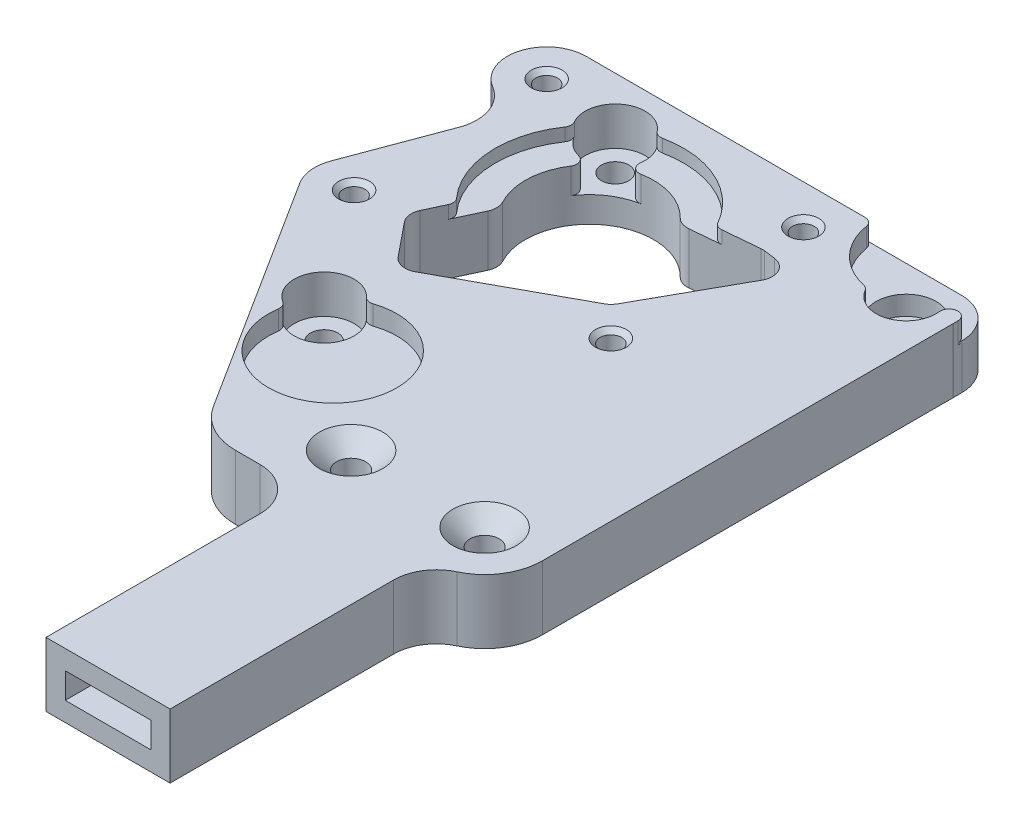
SolidWorks part; units mm, degrees
ref_plane "Front Plane" through (0, 0, 0) normal (0, 0, 1) x (1, 0, 0)
ref_plane "Top Plane" through (0, 0, 0) normal (0, 1, 0) x (1, 0, 0)
ref_plane "Right Plane" through (0, 0, 0) normal (1, 0, 0) x (0, 0, -1)
ref_plane "Plane1" through (0, 7.5, 0) normal (0, 1, 0) x (1, 0, 0)
sketch "Sketch1" plane through (0, 7.5, 0) normal (0, 1, 0) x (1, 0, 0)
  line L0 (33.5088, 30.3732) -> (33.4946, 33.0246)
  line L1 (28.8947, 37.6) -> (-15, 37.6)
  line L2 (-15.2354, 23.0047) -> (-20.1102, 9.9673)
  line L3 (-20.1102, 9.9673) -> (-10.6436, -4.9474)
  line L4 (-3.0147, -6.6193) -> (18.315, 7.1653)
  line L5 (18.315, 7.1653) -> (33.5088, 30.3732)
  line L6 (5.9537, 27.5611) -> (14.9094, 28.3729)
  line L7 (14.9094, 28.3729) -> (16.4399, 28.1735)
  line L8 (17.9289, 25.2174) -> (11.6276, 13.8992)
  line L9 (11.6276, 13.8992) -> (-4.6196, 5.0217)
  line L10 (-4.6196, 5.0217) -> (-9.6163, 11.1694)
  line L11 (-9.6163, 11.1694) -> (-6.1277, 18.6756)
  arc A0 (33.4946, 33.0246) -> (28.8947, 37.6) centre (28.8947, 33) ccw
  arc A1 (-15, 37.6) -> (-17.3569, 29.0497) centre (-15, 33) ccw
  arc A2 (-17.3569, 29.0497) -> (-15.2354, 23.0047) centre (-19.9187, 24.7558) cw
  arc A3 (-10.6436, -4.9474) -> (-3.0147, -6.6193) centre (-6, -2) ccw
  arc A4 (-6.1277, 18.6756) -> (5.9537, 27.5611) centre (0, 23) cw
  arc A5 (16.4399, 28.1735) -> (17.9289, 25.2174) centre (16.1815, 26.1903) cw
extrude "Boss-Extrude1" add sketch "Sketch1" against normal blind 7.5
sketch "Sketch2" plane through (0, 7.5, 0) normal (0, 1, 0) x (-1, 0, 0)
  line L0 (-33.4971, -32.5476) -> (-33.4946, -33.0246)
  arc A0 (-33.4946, -33.0246) -> (-33.4848, -32.699) centre (-28.8947, -33) cw
  arc A1 (-33.4848, -32.699) -> (-33.4971, -32.5476) centre (-32.4972, -32.5423) cw
extrude "Cut-Extrude1" cut sketch "Sketch2" against normal blind 2.45
sketch "Sketch3" plane through (0, 7.5, 0) normal (0, 1, 0) x (-1, 0, 0)
  line L0 (-28.8947, -37.6) -> (-18.4914, -37.6)
  arc A0 (-18.4914, -37.6) -> (-31.7305, -33.1844) centre (-25.9808, -38) ccw
  arc A1 (-31.7305, -33.1844) -> (-33.4848, -32.699) centre (-32.4972, -32.5423) cw
  arc A2 (-33.4848, -32.699) -> (-28.8947, -37.6) centre (-28.8947, -33) ccw
extrude "Cut-Extrude2" cut sketch "Sketch3" against normal blind 2.25
sketch "Sketch4" plane through (0, 7.5, 0) normal (0, 1, 0) x (-1, 0, 0)
  line L0 (-5.9537, -27.5611) -> (-9.8416, -27.9135)
  line L1 (7.7472, -15.191) -> (6.1277, -18.6756)
  arc A0 (-9.8416, -27.9135) -> (2.8936, -33.6126) centre (0, -23) ccw
  arc A1 (2.8936, -33.6126) -> (8.6833, -29.7528) centre (6, -32) ccw
  arc A2 (8.6833, -29.7528) -> (7.7472, -15.191) centre (0, -23) ccw
  arc A3 (6.1277, -18.6756) -> (-5.9537, -27.5611) centre (0, -23) cw
extrude "Cut-Extrude3" cut sketch "Sketch4" against normal blind 1.5
sketch "Sketch5" plane through (0, 6, 0) normal (0, 1, 0) x (-1, 0, 0)
  arc A0 (2.5358, -31.5008) -> (6.8716, -28.6103) centre (6, -32) ccw
  arc A1 (6.8716, -28.6103) -> (6.2829, -27.0957) centre (7.1207, -27.6418) cw
  arc A2 (6.2829, -27.0957) -> (1.3641, -30.3749) centre (0, -23) cw
  arc A3 (1.3641, -30.3749) -> (2.5358, -31.5008) centre (1.546, -31.3582) cw
extrude "Cut-Extrude4" cut sketch "Sketch5" against normal blind 3
sketch "Sketch6" plane through (0, 7.5, 0) normal (0, 1, 0) x (-1, 0, 0)
  line L0 (3.0147, 6.6193) -> (-5.0193, 1.4272)
  arc A0 (-5.0193, 1.4272) -> (3.0344, 0.1412) centre (0, 7) ccw
  arc A1 (3.0344, 0.1412) -> (7.8779, 4.9535) centre (6, 2) cw
  arc A2 (7.8779, 4.9535) -> (8.9511, 6.6413) centre (8.4145, 5.7974) cw
  arc A3 (8.9511, 6.6413) -> (3.0147, 6.6193) centre (6, 2) ccw
extrude "Cut-Extrude5" cut sketch "Sketch6" against normal blind 2.25
draft "Draft1" type of draft neutral plane draft angle 45 faces to draft 1 face at (33.4941, 5.05, -32.7572) neutral plane through (33.5088, 0, -30.3732) neutral plane normal (1, 0, -0.0054) parameters "D1"=45
ref_plane "Plane2" through (0, 0, -32) normal (0, 0, -1) x (-1, 0, 0)
sketch "Sketch7" plane through (0, 0, -32) normal (0, 0, -1) x (-1, 0, 0)
  line L0 (-29.6, 0) -> (-28, 0)
  line L1 (-28, 0) -> (-28, 7.5)
  line L2 (-28, 7.5) -> (-31.5, 7.5)
  line L3 (-31.5, 7.5) -> (-31.5, 3)
  line L4 (-31.5, 3) -> (-29.6, 3)
  line L5 (-29.6, 3) -> (-29.6, 0)
  line L6 (-28, 0) -> (-28, 7.5) construction
revolve "Cut-Revolve1" cut sketch "Sketch7" angle 360 about L6 reverse direction yes
ref_plane "Plane3" through (0, 0, 2) normal (0, 0, -1) x (-1, 0, 0)
sketch "Sketch8" plane through (0, 0, 2) normal (0, 0, -1) x (-1, 0, 0)
  line L0 (4.4, 0) -> (6, 0)
  line L1 (6, 0) -> (6, 7.5)
  line L2 (6, 7.5) -> (2.5, 7.5)
  line L3 (2.5, 7.5) -> (2.5, 3)
  line L4 (2.5, 3) -> (4.4, 3)
  line L5 (4.4, 3) -> (4.4, 0)
  line L6 (6, 0) -> (6, 7.5) construction
revolve "Cut-Revolve2" cut sketch "Sketch8" angle 360 about L6 reverse direction yes
hole_wizard "Ø3.2 (3.2) Diameter Hole1" positions "Sketch10" profile "Sketch9" hole size "Ø3.2" standard "ANSI Metric"
sketch "Sketch10" plane through (0, 3, 0) normal (0, 1, 0) x (1, 0, 0)
  point P0 (-6, 32)
sketch "Sketch9" plane through (-6, 3, -32) normal (1, 0, 0) x (0, 0, 1)
  line L0 (0, 0) -> (0, 3)
  line L1 (0, 3) -> (1.6, 3)
  line L2 (1.6, 3) -> (1.6, 0)
  line L5 (1.6, 0) -> (0, 0)
  line L11 (0, -6.35) -> (0, 107.95) construction
  dimension "Thru Hole Dia." = 3.2
  dimension "Thru Hole Depth" = 3
hole_wizard "M2 Clearance Hole1" positions "Sketch12" profile "Sketch11" hole size "M2" standard "ANSI Metric"
sketch "Sketch12" plane through (0, 7.5, 0) normal (0, 1, 0) x (1, 0, 0)
  point P0 (-15, 10.5)
  point P1 (15, 10.5)
sketch "Sketch11" plane through (-15, 7.5, -10.5) normal (1, 0, 0) x (0, 0, 1)
  line L0 (0, 0) -> (0, 7.5)
  line L1 (0, 7.5) -> (1.2645, 7.5)
  line L2 (1.2645, 7.5) -> (1.2645, 0)
  line L5 (1.2645, 0) -> (0, 0)
  line L11 (0, -6.35) -> (0, 107.95) construction
  dimension "Thru Hole Dia." = 2.529
  dimension "Thru Hole Depth" = 7.5
hole_wizard "M2 Clearance Hole2" positions "Sketch14" profile "Sketch13" hole size "M2" standard "ANSI Metric"
sketch "Sketch14" plane through (0, 0, 0) normal (0, -1, 0) x (-1, 0, 0)
  point P0 (15, 33)
  point P1 (-15, 33)
sketch "Sketch13" plane through (-15, 0, -33) normal (1, 0, 0) x (0, 0, -1)
  line L0 (0, 0) -> (0, 7.5)
  line L1 (0, 7.5) -> (1.2645, 7.5)
  line L2 (1.2645, 7.5) -> (1.2645, 0)
  line L5 (1.2645, 0) -> (0, 0)
  line L11 (0, -6.35) -> (0, 107.95) construction
  dimension "Thru Hole Dia." = 2.529
  dimension "Thru Hole Depth" = 7.5
fillet "Fillet1" radius 1 9 edges at (5.0193, 6.375, 1.4272) (-2.8936, 6.75, -33.6126) (-8.6833, 6.75, -29.7528) (31.403, 6.375, -32.8183) (18.4914, 6.375, -37.6) (24.7947, 6.375, -30.5944) (-7.7472, 6.75, -15.191) (-3.0344, 6.375, 0.1412) (9.8416, 6.75, -27.9135) tangent propagation no
fillet "Fillet2" radius 2 6 edges at (11.6276, 3.75, -13.8992) (-6.1277, 3, -18.6756) (-4.6196, 3.75, -5.0217) (5.9537, 3, -27.5611) (14.9094, 3.75, -28.3729) (-9.6163, 3.75, -11.1694) tangent propagation no
fillet "Fillet3" radius 4.6 2 edges at (-20.1102, 3.75, -9.9673) (18.315, 3.75, -7.1653) tangent propagation no
fillet "Fillet4" radius 5.5 1 edges at (33.5088, 3.75, -30.3732) tangent propagation no
chamfer "Chamfer2" distance 0.5355 angle 45 8 edges at (-15, 0, -9.2355) (15, 0, -9.2355) (15, 7.5, -34.2645) (-15, 7.5, -34.2645) (-15, 7.5, -9.2355) (-15, 0, -34.2645) (15, 0, -34.2645) (15, 7.5, -9.2355)
sketch "Sketch15" plane through (0, 7.5, 0) normal (0, 1, 0) x (1, 0, 0)
  line L0 (33.4999, 32.0295) -> (33.4999, -16)
  line L1 (26.7499, -22.75) -> (4.3666, -22.75)
  line L2 (-1.3323, -19.6172) -> (-10.6436, -4.9474)
  line L3 (-18.8837, 8.0349) -> (-10.6436, -4.9474) construction
  line L4 (11.15, -16) -> (26.75, -16) construction
  line L5 (-3.0147, -6.6193) -> (17.4968, 6.6366)
  line L6 (18.8486, 7.9804) -> (32.6016, 28.9874)
  circle A0 centre (26.75, -16) radius 1.7
  circle A1 centre (11.15, -16) radius 1.7
  circle A2 centre (-6, -2) radius 1.6 construction
  circle A3 centre (28, 32) radius 1.6 construction
  arc A4 (4.3666, -22.75) -> (-1.3323, -19.6172) centre (4.3666, -16) cw
  arc A5 (33.4999, -16) -> (26.7499, -22.75) centre (26.7499, -16) cw
  arc A6 (-10.6436, -4.9474) -> (-3.0147, -6.6193) centre (-6, -2) ccw
  arc A7 (17.4968, 6.6366) -> (18.8486, 7.9804) centre (15, 10.5) ccw
  arc A8 (32.6016, 28.9874) -> (33.4999, 32.0295) centre (28, 32) ccw construction
  arc A9 (32.6016, 28.9874) -> (33.4999, 32.0295) centre (27.9003, 32.0295) ccw
  dimension "D1" = 15.6
  dimension "D2" = 17.15
  dimension "D3" = 48
  dimension "D4" = 6.75
  dimension "D5" = 6.75
  dimension "D6" = 3.4
  dimension "D7" = 3.4
extrude "Boss-Extrude2" add sketch "Sketch15" against normal up to surface (7.5 mm away) up to face at (-15, 0, -8.7)
sketch "Sketch16" plane through (0, 5.25, 0) normal (0, 1, 0) x (1, 0, 0)
  circle A0 centre (0, -7) radius 7.5
  arc A1 (4.4901, -0.9926) -> (-2.3826, 0.1115) centre (0, -7) ccw construction
extrude "Cut-Extrude6" cut sketch "Sketch16" along normal through all
sketch "Sketch17" plane through (0, 5.25, 0) normal (0, 1, 0) x (1, 0, 0)
  line L0 (5.6316, -1.0315) -> (5.0193, -1.4272)
  arc A0 (-7.4246, -5.9389) -> (-7.4943, -7.2931) centre (0, -7) ccw
  arc A1 (-7.4943, -7.2931) -> (-8.9511, -6.6413) centre (-6, -2) cw
  arc A2 (4.4901, -0.9926) -> (5.6316, -1.0315) centre (5.0888, -0.1916) ccw
  arc A3 (-8.9511, -6.6413) -> (-7.4246, -5.9389) centre (-8.4145, -5.7974) ccw
  arc A5 (5.0193, -1.4272) -> (4.4901, -0.9926) centre (0, -7) ccw
extrude "Boss-Extrude3" add sketch "Sketch17" along normal up to surface (2.25 mm away) up to face at (-1.5875, 7.5, 3.6036)
chamfer "Chamfer3" distance 2 angle 45 2 edges at (11.15, 7.5, 17.7) (26.75, 7.5, 17.7)
sketch "Sketch18" plane through (0, 0, 22.75) normal (0, 0, 1) x (1, 0, 0)
  line L0 (26.7499, 0) -> (4.3666, 0) construction
  line L1 (26.7499, 7.5) -> (12.2499, 7.5)
  line L2 (26.7499, 7.5) -> (26.7499, 0)
  line L3 (26.7499, 0) -> (12.2499, 0)
  line L4 (12.2499, 7.5) -> (12.2499, 0)
  line L6 (24.4999, 5.25) -> (14.4999, 5.25)
  line L7 (24.4999, 5.25) -> (24.4999, 2.25)
  line L8 (24.4999, 2.25) -> (14.4999, 2.25)
  line L9 (14.4999, 5.25) -> (14.4999, 2.25)
  point P11 (26.7499, 3.75)
  dimension "D1" = 3
  dimension "D2" = 2.25
  dimension "D3" = 2.25
  dimension "D4" = 2.25
  dimension "D5" = 10
extrude "Boss-Extrude4" add sketch "Sketch18" along normal blind 30
fillet "Fillet5" radius 5 2 edges at (12.2499, 3.75, 22.75) (26.7499, 3.75, 22.75)
